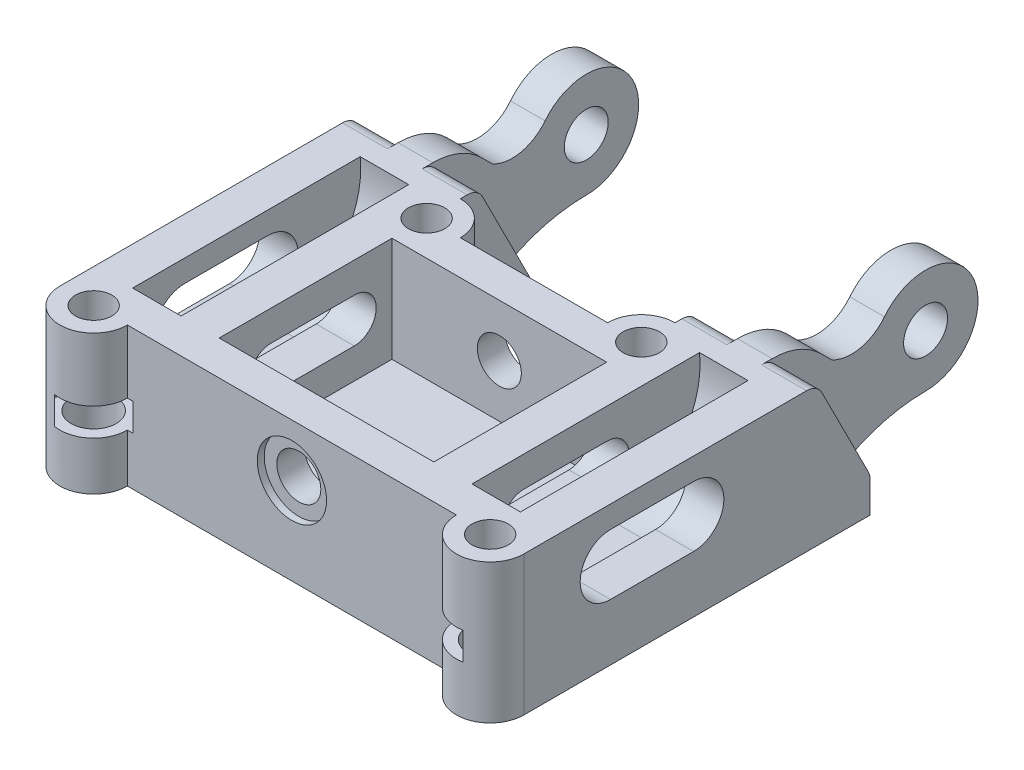
SolidWorks part; units mm, degrees
material "ABS"
ref_plane "Front Plane" through (0, 0, 0) normal (0, 0, 1) x (1, 0, 0)
ref_plane "Top Plane" through (0, 0, 0) normal (0, 1, 0) x (1, 0, 0)
ref_plane "Right Plane" through (0, 0, 0) normal (1, 0, 0) x (0, 0, -1)
sketch "Sketch1" plane through (0, 0, 0) normal (1, 0, 0) x (0, 0, -1)
  line L0 (0, 0) -> (-52, 0) construction
  line L1 (-52, 0) -> (-40, 0) construction
  line L2 (-52, 0) -> (-40, 0) construction
  line L3 (-52, 3.175) -> (-40, 3.175)
  line L4 (-52, -3.175) -> (-40, -3.175)
  line L7 (-14.5, -12.57) -> (-14.5, -7.57) construction
  line L14 (-64.5, -12.57) -> (-14.5, -12.57)
  line L18 (-13.5364, 3.0946) -> (-28.8864, 3.0946) construction
  line L19 (-13.5364, 3.0946) -> (-15.0829, 4.6411)
  line L20 (-24.4811, 7.57) -> (-22.1539, 7.57)
  line L23 (-64.5, 7.57) -> (-64.5, -12.57)
  line L24 (-64.5, 7.57) -> (-24.4811, 7.57)
  circle A0 centre (0, 0) radius 3.175
  arc A2 (-52, 3.175) -> (-52, -3.175) centre (-52, 0) ccw
  arc A3 (-40, -3.175) -> (-40, 3.175) centre (-40, 0) ccw
  arc A4 (-13.5364, 3.0946) -> (-5.9378, 4.6955) centre (-10.699, 8.4606) ccw
  arc A5 (0, -7.57) -> (-5.9378, 4.6955) centre (0, 0) ccw
  arc A6 (-14.5, -12.57) -> (0, -7.57) centre (0, -31.095) cw
  arc A10 (-22.1539, 7.57) -> (-15.0829, 4.6411) centre (-22.1539, -2.43) cw
  point P6 (-46, 0)
  point P22 (-22, 7.57)
  point P26 (-64.5, 7.57)
  dimension "D1" = 6.35
  dimension "D2" = 7.57
  dimension "D5" = 3.175
  dimension "D13" = 6.07
  dimension "D14" = 45
  dimension "D15" = 3.0946
  dimension "D16" = 10
  dimension "D3" = 52
  dimension "D4" = 12
  dimension "D10" = 50
  dimension "D11" = 5
extrude "Boss-Extrude1" add sketch "Sketch1" along normal blind 18
ref_plane "Plane1" through (9, 0, 0) normal (-1, 0, 0) x (0, 0, 1)
sketch "Sketch7" plane through (9, 0, 0) normal (-1, 0, 0) x (0, 0, 1)
  line L1 (68.6836, -7.57) -> (38.8542, -7.57)
  line L2 (68.6836, -7.57) -> (68.6836, 7.57)
  line L5 (64.5, -12.57) -> (14.5, -12.57) construction
  line L6 (26.6391, 7.57) -> (68.6836, 7.57)
  arc A0 (26.6391, 7.57) -> (38.8542, -7.57) centre (40.3166, 6.1075) ccw
  dimension "D1" = 5
extrude "Cut-Extrude4" cut sketch "Sketch7" against normal blind 3.5 and the other way blind 3.5
sketch "Sketch8" plane through (18, 0, 0) normal (1, 0, 0) x (0, 0, -1)
  line L35 (-26.5145, 0) -> (-3.762, 0) construction
  line L48 (-14.5, -12.57) -> (-14.5, -7.57)
  line L49 (-14.5, -7.57) -> (-22.1539, 7.57)
  line L50 (-14.5, -12.57) -> (7.3862, -6.3582)
  line L51 (7.3862, -6.3582) -> (9.4111, 3.26)
  line L52 (9.4111, 3.26) -> (4.2477, 15.2069)
  line L53 (4.2477, 15.2069) -> (-22.1539, 7.57)
  dimension "D1" = 0
  dimension "D2" = 5
extrude "Cut-Extrude5" cut sketch "Sketch8" against normal blind 6.5
sketch "Sketch9" plane through (0, 0, 0) normal (-1, 0, 0) x (0, 0, 1)
  line L0 (64.5, 7.57) -> (64.5, -12.57) construction
  line L1 (14.5, -12.57) -> (64.5, -12.57)
  line L2 (14.5, -12.57) -> (14.5, -7.57)
  line L3 (14.5, -7.57) -> (64.5, -7.57)
  line L4 (64.5, -12.57) -> (64.5, -7.57)
  dimension "D1" = 0
extrude "Boss-Extrude2" add sketch "Sketch9" along normal blind 15.5
mirror "Mirror2" about plane through (9, 0, 0) normal (-1, 0, 0) of "Cut-Extrude5"
fillet "Fillet8" radius 2.5 3 edges at (3.25, 7.57, 22.1539) (14.75, -7.57, 14.5) (14.75, 7.57, 22.1539)
sketch "Sketch13" plane through (18, 0, 0) normal (1, 0, 0) x (0, 0, -1)
  line L0 (-23.6914, 7.57) -> (-64.5, 7.57) construction
  line L1 (-64.5, -7.57) -> (-59.5, -7.57)
  line L2 (-64.5, -7.57) -> (-64.5, 7.57)
  line L3 (-64.5, 7.57) -> (-59.5, 7.57)
  line L4 (-59.5, -7.57) -> (-59.5, 7.57)
  dimension "D1" = 5
extrude "Boss-Extrude3" add sketch "Sketch13" against normal up to surface (33.5 mm away) up to face at (-15.5, -10.07, 39.5)
sketch "Sketch16" plane through (0, -7.57, 0) normal (0, 1, 0) x (1, 0, 0)
  line L0 (-15.5, -34.55) -> (50.0191, -34.55) construction
  line L1 (-15.5, -59.5) -> (-15.5, -14.5) construction
  line L2 (-15.5, -14.5) -> (0, -14.5) construction
  line L3 (0, -59.5) -> (0, -14.5) construction
  line L4 (-15.5, -34.55) -> (0, -34.55)
  line L5 (-15.5, -34.55) -> (-15.5, -29.55)
  line L6 (-15.5, -29.55) -> (0, -29.55)
  line L7 (0, -34.55) -> (0, -29.55)
  dimension "D1" = 20.05
  dimension "D2" = 5
extrude "Boss-Extrude4" add sketch "Sketch16" along normal up to surface (15.14 mm away) up to face at (9, 7.57, 43.0696)
sketch "Sketch14" plane through (0, 0, 64.5) normal (0, 0, 1) x (1, 0, 0)
  line L0 (-15.5, -12.57) -> (-15.5, 7.57) construction
  line L1 (-15.5, 3.175) -> (-15.5, -3.175)
  line L2 (18, 7.57) -> (-15.5, 7.57) construction
  arc A0 (-15.5, -3.175) -> (-15.5, 3.175) centre (-15.5, 0) ccw
  dimension "D1" = 6.35
  dimension "D2" = 7.57
extrude "Cut-Extrude8" cut sketch "Sketch14" against normal up to surface (34.95 mm away) up to face at (-7.75, 0, 29.55)
sketch "Sketch17" plane through (18, 0, 0) normal (1, 0, 0) x (0, 0, -1)
  line L0 (-40, 0) -> (-52, 0) construction
  line L1 (-40, -4.375) -> (-52, -4.375)
  line L2 (-40, 4.375) -> (-52, 4.375)
  arc A0 (-40, -4.375) -> (-40, 4.375) centre (-40, 0) ccw
  arc A1 (-52, 4.375) -> (-52, -4.375) centre (-52, 0) ccw
  point P4 (-46, 0)
  dimension "D1" = 4.375
extrude "Cut-Extrude9" cut sketch "Sketch17" against normal up to surface (5.5 mm away) up to face at (12.5, -0.6325, 45.3394)
sketch "Sketch19" plane through (0, 0, 64.5) normal (0, 0, 1) x (1, 0, 0)
  line L0 (-15.5, 5) -> (-15.5, -5)
  arc A0 (-15.5, -5) -> (-15.5, 5) centre (-15.5, 0) ccw
  dimension "D1" = 10
extrude "Cut-Extrude10" cut sketch "Sketch19" against normal blind 1
sketch "Sketch20" plane through (0, 0, 29.55) normal (0, 0, -1) x (-1, 0, 0)
  circle A1 centre (15.5, 0) radius 5
  dimension "D1" = 10
extrude "Cut-Extrude11" cut sketch "Sketch20" against normal blind 1
mirror "Mirror3" about plane through (-15.5, 0, 0) normal (1, 0, 0) of bodies 120 113
sketch "Sketch21" plane through (0, -7.57, 0) normal (0, 1, 0) x (1, 0, 0)
  line L1 (0, -14.5) -> (-31, -14.5)
  line L2 (0, -14.5) -> (0, -29.55)
  line L3 (0, -29.55) -> (-31, -29.55)
  line L4 (-31, -14.5) -> (-31, -29.55)
extrude "Cut-Extrude12" cut sketch "Sketch21" against normal up to surface (5 mm away) up to face at (-15.5, -12.57, 27)
sketch "Sketch30" plane through (0, 7.57, 0) normal (0, 1, 0) x (1, 0, 0)
  line L0 (0, -24.675) -> (0, -27.425)
  line L1 (18, -64.5) -> (-49, -64.5) construction
  line L2 (-2.125, -29.55) -> (-4.875, -29.55)
  line L3 (11, -64.5) -> (8.25, -64.5)
  line L4 (15.25, -64.5) -> (18, -64.5)
  line L5 (-15.5, -29.55) -> (-15.5, -64.5) construction
  line L6 (-31, -29.55) -> (0, -29.55) construction
  line L7 (-42, -64.5) -> (-39.25, -64.5)
  line L8 (-46.25, -64.5) -> (-49, -64.5)
  arc A0 (0, -27.425) -> (-2.125, -29.55) centre (0, -29.55) ccw
  arc A1 (0, -24.675) -> (-4.875, -29.55) centre (0, -29.55) ccw
  arc A2 (15.25, -64.5) -> (11, -64.5) centre (13.125, -64.5) cw
  arc A3 (18, -64.5) -> (8.25, -64.5) centre (13.125, -64.5) cw
  arc A4 (-46.25, -64.5) -> (-42, -64.5) centre (-44.125, -64.5) ccw
  arc A5 (-49, -64.5) -> (-39.25, -64.5) centre (-44.125, -64.5) ccw
  dimension "D1" = 4.25
  dimension "D2" = 4.875
  dimension "D3" = 2.125
  dimension "D4" = 4.875
extrude "Boss-Extrude11" add sketch "Sketch30" against normal up to surface (20.14 mm away) up to face at (-15.5, -12.57, 25.3417)
sketch "Sketch31" plane through (0, 7.57, 0) normal (0, 1, 0) x (1, 0, 0)
  line L0 (15.25, -64.5) -> (11, -64.5) construction
  line L1 (-42, -64.5) -> (-46.25, -64.5) construction
  circle A0 centre (0, -29.55) radius 2.125
  circle A1 centre (13.125, -64.5) radius 2.125
  circle A2 centre (-44.125, -64.5) radius 2.125
  dimension "D3" = 4.25
  dimension "D4" = 4.25
  dimension "D5" = 4.25
  dimension "D1" = 34.95
  dimension "D2" = 13.125
extrude "Cut-Extrude16" cut sketch "Sketch31" against normal up to surface (20.14 mm away) up to face at (-14.859, -12.57, 31.101)
ref_plane "Plane2" through (-15.5, 0, 0) normal (1, 0, 0) x (0, 0, -1)
mirror "Mirror4" about plane through (-15.5, 0, 0) normal (1, 0, 0) of "Cut-Extrude16", "Boss-Extrude11"
sketch "Sketch34" plane through (0, -12.57, 0) normal (0, -1, 0) x (1, 0, 0)
  circle A0 centre (-31, 29.55) radius 6.35
  arc A1 (-31, 24.675) -> (-26.125, 29.55) centre (-31, 29.55) ccw construction
  circle A2 centre (-44.125, 64.5) radius 6.35
  arc A3 (-39.25, 64.5) -> (-49, 64.5) centre (-44.125, 64.5) ccw construction
  circle A4 centre (13.125, 64.5) radius 6.35
  arc A5 (18, 64.5) -> (8.25, 64.5) centre (13.125, 64.5) ccw construction
  circle A6 centre (0, 29.55) radius 6.35
  arc A7 (-4.875, 29.55) -> (0, 24.675) centre (0, 29.55) ccw construction
  dimension "D1" = 12.7
ref_plane "Plane3" through (0, -2.57, 0) normal (0, -1, 0) x (-1, 0, 0)
sketch "Sketch32" plane through (0, -2.57, 0) normal (0, -1, 0) x (1, 0, 0)
  line L0 (-26.1548, 22.1338) -> (-22.1548, 29.062)
  line L1 (-31, 34.1688) -> (-35, 31.8594)
  line L2 (-35, 31.8594) -> (-35, 27.2406)
  line L3 (-35, 27.2406) -> (-26.1548, 22.1338)
  line L6 (-22.1548, 29.062) -> (-31, 34.1688)
  line L25 (-29, 26.0859) -> (-27.25, 27.0963) [skipped]
  line L26 (-27, 29.55) -> (-27, 31.5707) [skipped]
  line L28 (-15.5, 64.5) -> (-15.5, 29.55) construction
  line L29 (-26.125, 29.55) -> (-4.875, 29.55) construction
  line L31 (-44.125, 64.5) -> (-26.1548, 64.5) construction
  line L34 (11.9296, 60.0386) -> (8.6636, 63.3046)
  line L35 (16.391, 61.234) -> (11.9296, 60.0386)
  line L36 (-45.3204, 68.9614) -> (-48.5864, 65.6954)
  line L37 (-48.5864, 65.6954) -> (-47.391, 61.234)
  line L38 (-47.391, 61.234) -> (-42.9296, 60.0386)
  line L39 (-42.9296, 60.0386) -> (-39.6636, 63.3046)
  line L41 (8.25, 64.5) -> (-39.25, 64.5) construction
  line L42 (-45.3204, 68.9614) -> (-38.8388, 75.443)
  line L43 (-38.8388, 75.443) -> (-33.1737, 69.7779)
  line L44 (-33.1737, 69.7779) -> (-39.6636, 63.3046)
  line L45 (-40.859, 67.766) -> (-45.3204, 68.9614) [skipped]
  line L46 (-39.6636, 63.3046) -> (-40.859, 67.766) [skipped]
  line L47 (17.5864, 65.6954) -> (16.391, 61.234)
  line L48 (14.3204, 68.9614) -> (17.5864, 65.6954)
  line L49 (14.3204, 68.9614) -> (7.8388, 75.443)
  line L50 (7.8388, 75.443) -> (2.1737, 69.7779)
  line L51 (2.1737, 69.7779) -> (8.6636, 63.3046)
  line L52 (4, 27.2406) -> (-4.8452, 22.1338)
  line L53 (4, 31.8594) -> (4, 27.2406)
  line L54 (0, 34.1688) -> (4, 31.8594)
  line L55 (-8.8452, 29.062) -> (0, 34.1688)
  line L56 (-4.8452, 22.1338) -> (-8.8452, 29.062)
  arc A0 (-29, 33.0141) -> (-33, 26.0859) centre (-31, 29.55) ccw construction
  circle A1 centre (-44.125, 64.5) radius 4 construction
  dimension "D1" = 8
  dimension "D2" = 135
  dimension "D3" = 8
sketch "Sketch37" plane through (0, -12.57, 0) normal (0, -1, 0) x (1, 0, 0)
  line L12 (8.25, 64.5) -> (-39.25, 64.5)
  line L13 (-49, 64.5) -> (-49, 14.5)
  line L14 (-49, 14.5) -> (-42.5, 14.5)
  line L15 (-42.5, 14.5) -> (-37.5, 14.5)
  line L16 (-37.5, 14.5) -> (-31, 14.5)
  line L17 (-31, 14.5) -> (-31, 24.675)
  line L18 (-26.125, 29.55) -> (-4.875, 29.55)
  line L19 (0, 24.675) -> (0, 14.5)
  line L20 (0, 14.5) -> (6.5, 14.5)
  line L21 (6.5, 14.5) -> (11.5, 14.5)
  line L22 (11.5, 14.5) -> (18, 14.5)
  line L23 (18, 14.5) -> (18, 64.5)
  line L24 (8.25, 64.5) -> (-39.25, 64.5)
  line L25 (-49, 64.5) -> (-49, 14.5)
  line L26 (-49, 14.5) -> (-42.5, 14.5)
  line L27 (-42.5, 14.5) -> (-37.5, 14.5)
  line L28 (-37.5, 14.5) -> (-31, 14.5)
  line L29 (-31, 14.5) -> (-31, 24.675)
  line L30 (-26.125, 29.55) -> (-4.875, 29.55)
  line L31 (0, 24.675) -> (0, 14.5)
  line L32 (0, 14.5) -> (6.5, 14.5)
  line L33 (6.5, 14.5) -> (11.5, 14.5)
  line L34 (11.5, 14.5) -> (18, 14.5)
  line L35 (18, 14.5) -> (18, 64.5)
  arc A4 (18, 64.5) -> (8.25, 64.5) centre (13.125, 64.5) ccw
  arc A5 (-39.25, 64.5) -> (-49, 64.5) centre (-44.125, 64.5) ccw
  arc A6 (-31, 24.675) -> (-26.125, 29.55) centre (-31, 29.55) ccw
  arc A7 (-4.875, 29.55) -> (0, 24.675) centre (0, 29.55) ccw
  arc A8 (18, 64.5) -> (8.25, 64.5) centre (13.125, 64.5) ccw
  arc A9 (-39.25, 64.5) -> (-49, 64.5) centre (-44.125, 64.5) ccw
  arc A10 (-31, 24.675) -> (-26.125, 29.55) centre (-31, 29.55) ccw
  arc A11 (-4.875, 29.55) -> (0, 24.675) centre (0, 29.55) ccw
  dimension "D1" = 0
sketch "Sketch38" plane through (0, -12.57, 0) normal (0, -1, 0) x (1, 0, 0)
  circle A0 centre (-31, 29.55) radius 3.25
  circle A1 centre (0, 29.55) radius 3.25
  circle A2 centre (13.125, 64.5) radius 3.25
  circle A3 centre (-44.125, 64.5) radius 3.25
  dimension "D1" = 6.5
  dimension "D2" = 6.5
  dimension "D3" = 6.5
  dimension "D4" = 6.5
extrude "Cut-Extrude19" cut sketch "Sketch38" against normal blind 8
extrude "Cut-Extrude21" cut sketch "Sketch32" against normal blind 1 and the other way blind 3
sketch "Sketch39" plane through (0, 7.57, 0) normal (0, 1, 0) x (1, 0, 0)
  circle A0 centre (-31, -29.55) radius 2.625
  circle A1 centre (0, -29.55) radius 2.625
  circle A2 centre (13.125, -64.5) radius 2.625
  circle A3 centre (-44.125, -64.5) radius 2.625
  dimension "D1" = 5.25
  dimension "D2" = 5.25
  dimension "D3" = 5.25
  dimension "D4" = 5.25
extrude "M5_Cut" cut sketch "Sketch39" against normal up to surface (9.14 mm away) up to face at (13.125, -1.57, 66.625)
